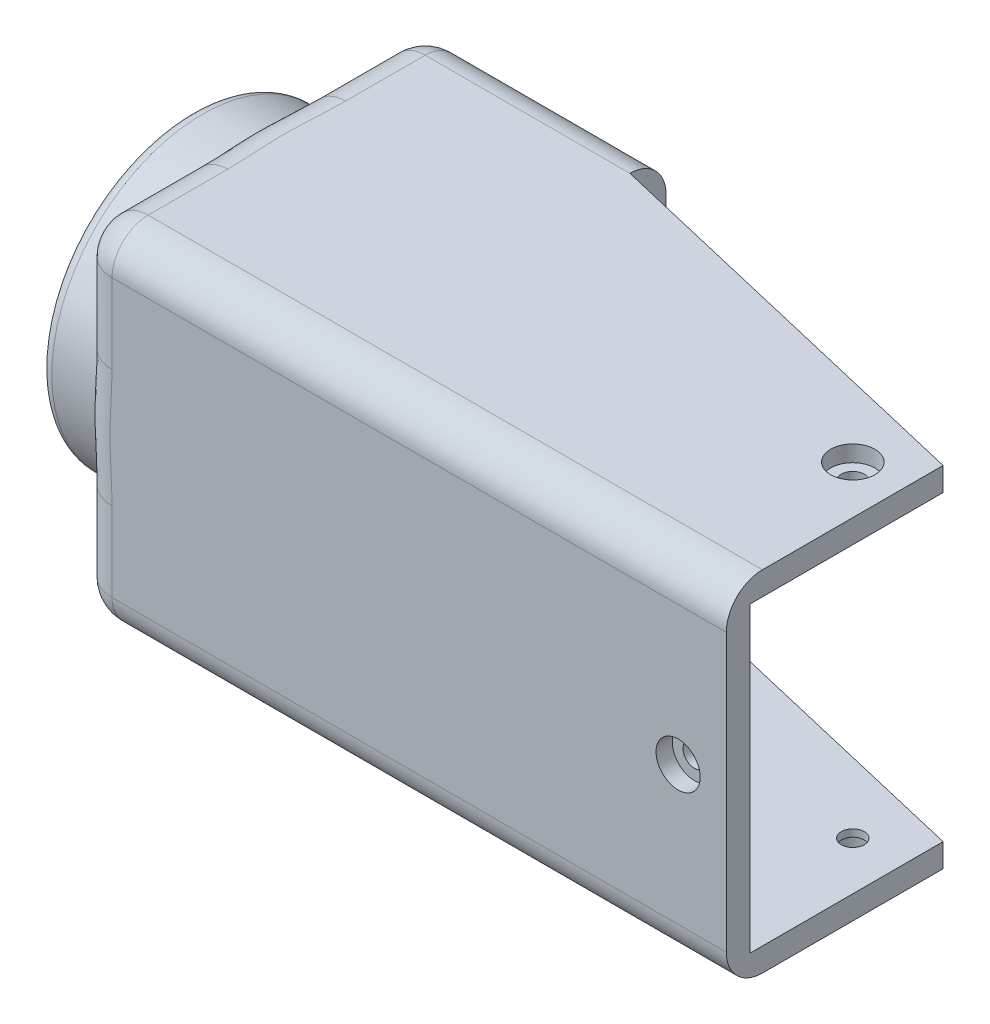
SolidWorks part; units mm, degrees
ref_plane "前视基准面" through (0, 0, 0) normal (0, 0, 1) x (1, 0, 0)
ref_plane "上视基准面" through (0, 0, 0) normal (0, 1, 0) x (1, 0, 0)
ref_plane "右视基准面" through (0, 0, 0) normal (1, 0, 0) x (0, 0, -1)
other "Configuration Table"
sketch "草图1" plane through (0, 0, 0) normal (1, 0, 0) x (0, 0, -1)
  line L1 (-20.488, -14.9861) -> (8.512, -14.9861)
  line L2 (-20.488, -14.9861) -> (-20.488, 14.0139)
  line L3 (-20.488, 14.0139) -> (8.512, 14.0139)
  line L4 (8.512, -14.9861) -> (8.512, 14.0139)
  line L5 (-20.488, -14.9861) -> (8.512, 14.0139) construction
  line L6 (-20.488, 14.0139) -> (8.512, -14.9861) construction
  circle A0 centre (-5.988, -0.4861) radius 12.5
  circle A1 centre (-5.988, -0.4861) radius 4
  circle A2 centre (-5.988, 7.5139) radius 2.5
  circle A3 centre (-5.988, 7.5139) radius 3.1
  circle A10 centre (2.012, -0.4861) radius 2.5
  circle A11 centre (2.012, -0.4861) radius 3.1
  circle A12 centre (-5.988, -8.4861) radius 2.5
  circle A13 centre (-5.988, -8.4861) radius 3.1
  circle A14 centre (-13.988, -0.4861) radius 2.5
  circle A15 centre (-13.988, -0.4861) radius 3.1
  point P24 (-3.237, 2.7509)
  point P25 (-5.988, -0.4861)
  dimension "D1" = 25
  dimension "D2" = 8
  dimension "D3" = 5
  dimension "D4" = 6.2
  dimension "D5" = 8
  dimension "D6" = 29
  dimension "D7" = 4
extrude "凸台-拉伸1" add sketch "草图1" along normal blind 7.8 contours A0
extrude "凸台-拉伸2" add sketch "草图1<3>" along normal blind 54 from offset 5 contours L3 L4 L1 L2 | A0
sketch "草图1<3>" plane through (0, 0, 0) normal (1, 0, 0) x (0, 0, -1) same geometry as "草图1"
extrude "切除-拉伸1" cut sketch "草图1<4>" along normal up to next contours A2 | A10 | A12 | A14 | A1 region at (0, -0.4861, 5.988) region at (0, 7.5139, 5.988) region at (0, -0.4861, -2.012) region at (0, -8.4861, 5.988) region at (0, -0.4861, 13.988)
sketch "草图1<4>" plane through (0, 0, 0) normal (1, 0, 0) x (0, 0, -1) same geometry as "草图1"
extrude "切除-拉伸2" cut sketch "草图1<5>" along normal blind 1.5 contours A11 A10 | A3 A2 | A15 A14 | A13 A12 region at (0, 7.5139, 9.0003) region at (0, -0.4861, 1.0003) region at (0, -8.4861, 9.0003) region at (0, -0.4861, 17.0003)
sketch "草图1<5>" plane through (0, 0, 0) normal (1, 0, 0) x (0, 0, -1) same geometry as "草图1"
extrude "切除-拉伸3" cut sketch "草图1<6>" against normal blind 1.5 from surface contours A3 A2 | A15 A14 | A11 A10 | A13 A12 region at (0, 7.5139, 9.0003) region at (0, -0.4861, 1.0003) region at (0, -8.4861, 9.0003) region at (0, -0.4861, 17.0003) starting at face at (7.8, 7.5139, 3.488)
sketch "草图1<6>" plane through (0, 0, 0) normal (1, 0, 0) x (0, 0, -1) same geometry as "草图1"
sketch "草图2" plane through (59, 0, 0) normal (1, 0, 0) x (0, 0, -1)
  line L1 (-18.538, 12.0639) -> (6.562, 12.0639)
  line L2 (-18.538, 12.0639) -> (-18.538, -13.0361)
  line L3 (-18.538, -13.0361) -> (6.562, -13.0361)
  line L4 (6.562, 12.0639) -> (6.562, -13.0361)
  line L5 (-18.538, 12.0639) -> (6.562, -13.0361) construction
  line L6 (-18.538, -13.0361) -> (6.562, 12.0639) construction
  point P0 (-5.988, -0.4861)
  dimension "D1" = 25.1
extrude "切除-拉伸4" cut sketch "草图2" against normal blind 40
fillet "圆角1" radius 3 4 edges at (32, 14.0139, 20.488) (32, -14.9861, 20.488) (32, 14.0139, -8.512) (32, -14.9861, -8.512)
fillet "圆角2" radius 3 8 edges at (5, -14.1074, -7.6333) (5, -14.9861, 5.988) (5, -14.1074, 19.6093) (5, -0.4861, 20.488) (5, 13.1352, 19.6093) (5, 14.0139, 5.988) (5, 13.1352, -7.6333) (5, -0.4861, -8.512)
fillet "圆角4" radius 1 1 edges at (0, -0.4861, -6.512)
hole_wizard "孔1" positions "草图3" profile "草图4" legacy
sketch "草图3" plane through (0, 0, -8.512) normal (0, 0, -1) x (-1, 0, 0)
  line L0 (-59, -11.9861) -> (-59, 11.0139) construction
  line L1 (-55, 11.0139) -> (-55, -11.9861)
  line L2 (-8, 11.0139) -> (-59, 11.0139) construction
  line L3 (-59, -11.9861) -> (-8, -11.9861) construction
  point P0 (-55, -0.4861)
  dimension "D1" = 4
sketch "草图4" plane through (55, -0.4861, -8.512) normal (1, 0, 0) x (0, 1, 0)
  line L0 (0, 0) -> (0, 4)
  line L1 (0, 4) -> (0.95, 4)
  line L2 (0.95, 4) -> (0.95, 1.35)
  line L3 (0.95, 1.35) -> (1.835, 1.35)
  line L4 (1.835, 1.35) -> (1.835, 0)
  line L5 (1.835, 0) -> (0, 0)
  line L6 (0, 110) -> (0, -10) construction
  dimension "直径" = 1.9
  dimension "深度" = 4
  dimension "柱坑直径" = 3.67
  dimension "柱坑深度" = 1.35
hole_wizard "孔2" positions "草图5" profile "草图6" legacy
sketch "草图5" plane through (0, -14.9861, 0) normal (0, -1, 0) x (-1, 0, 0)
  line L0 (-59, -17.488) -> (-59, 5.512) construction
  line L1 (-55, 5.512) -> (-55, -17.488)
  line L2 (-8, 5.512) -> (-59, 5.512) construction
  line L3 (-59, -17.488) -> (-8, -17.488) construction
  point P0 (-55, -5.988)
  dimension "D1" = 4
sketch "草图6" plane through (55, -14.9861, 5.988) normal (1, 0, 0) x (0, 0, -1)
  line L0 (0, 0) -> (0, 4)
  line L1 (0, 4) -> (0.95, 4)
  line L2 (0.95, 4) -> (0.95, 1.35)
  line L3 (0.95, 1.35) -> (1.835, 1.35)
  line L4 (1.835, 1.35) -> (1.835, 0)
  line L5 (1.835, 0) -> (0, 0)
  line L6 (0, 110) -> (0, -10) construction
  dimension "直径" = 1.9
  dimension "深度" = 4
  dimension "柱坑直径" = 3.67
  dimension "柱坑深度" = 1.35
hole_wizard "孔3" positions "草图7" profile "草图8" legacy
sketch "草图7" plane through (0, 0, 20.488) normal (0, 0, 1) x (1, 0, 0)
  line L0 (59, -11.9861) -> (59, 11.0139) construction
  line L1 (55, 11.0139) -> (55, -11.9861)
  line L2 (59, 11.0139) -> (8, 11.0139) construction
  line L3 (8, -11.9861) -> (59, -11.9861) construction
  point P0 (55, -0.4861)
  dimension "D1" = 4
sketch "草图8" plane through (55, -0.4861, 20.488) normal (1, 0, 0) x (0, -1, 0)
  line L0 (0, 0) -> (0, 4)
  line L1 (0, 4) -> (0.95, 4)
  line L2 (0.95, 4) -> (0.95, 1.35)
  line L3 (0.95, 1.35) -> (1.835, 1.35)
  line L4 (1.835, 1.35) -> (1.835, 0)
  line L5 (1.835, 0) -> (0, 0)
  line L6 (0, 110) -> (0, -10) construction
  dimension "直径" = 1.9
  dimension "深度" = 4
  dimension "柱坑直径" = 3.67
  dimension "柱坑深度" = 1.35
hole_wizard "孔4" positions "草图9" profile "草图10" legacy
sketch "草图9" plane through (0, 14.0139, 0) normal (0, 1, 0) x (1, 0, 0)
  line L0 (59, -17.488) -> (59, 5.512) construction
  line L1 (55, 5.512) -> (55, -17.488)
  line L2 (59, 5.512) -> (8, 5.512) construction
  line L3 (8, -17.488) -> (59, -17.488) construction
  point P0 (55, -5.988)
  dimension "D1" = 4
sketch "草图10" plane through (55, 14.0139, 5.988) normal (1, 0, 0) x (0, 0, 1)
  line L0 (0, 0) -> (0, 4)
  line L1 (0, 4) -> (0.95, 4)
  line L2 (0.95, 4) -> (0.95, 1.35)
  line L3 (0.95, 1.35) -> (1.835, 1.35)
  line L4 (1.835, 1.35) -> (1.835, 0)
  line L5 (1.835, 0) -> (0, 0)
  line L6 (0, 110) -> (0, -10) construction
  dimension "直径" = 1.9
  dimension "深度" = 4
  dimension "柱坑直径" = 3.67
  dimension "柱坑深度" = 1.35
sketch "草图11" plane through (0, 0, -8.512) normal (0, 0, -1) x (-1, 0, 0)
  line L0 (-8, -14.9861) -> (-59, -14.9861) construction
  line L1 (-59, 14.0139) -> (-25, 14.0139)
  line L2 (-59, 14.0139) -> (-59, -14.9861)
  line L3 (-59, -14.9861) -> (-25, -14.9861)
  line L4 (-25, 14.0139) -> (-25, -14.9861)
  dimension "D1" = 34
extrude "切除-拉伸5" cut sketch "草图11" against normal blind 3
sketch "草图12" plane through (0, -14.9861, 0) normal (0, -1, 0) x (1, 0, 0)
  line L0 (59, -5.512) -> (59, 2.488)
  line L1 (59, 17.488) -> (59, -5.512) construction
  line L2 (59, 2.488) -> (25, -5.512)
  line L3 (25, -5.512) -> (59, -5.512)
  dimension "D1" = 8
extrude "切除-拉伸6" cut sketch "草图12" against normal through all
